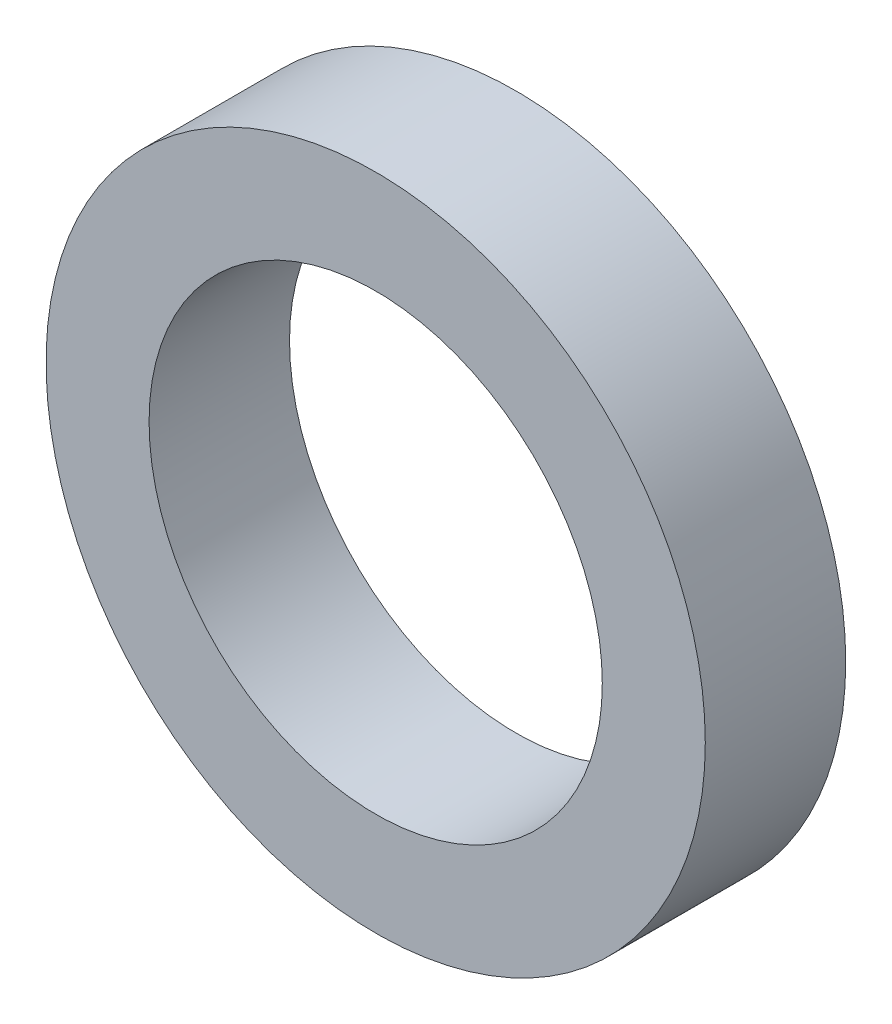
SolidWorks part; units mm, degrees
ref_plane "Front" through (0, 0, 0) normal (0, 0, 1) x (1, 0, 0)
ref_plane "Top" through (0, 0, 0) normal (0, 1, 0) x (1, 0, 0)
ref_plane "Right" through (0, 0, 0) normal (1, 0, 0) x (0, 0, -1)
sketch "Sketch1" plane through (0, 0, 0) normal (0, 0, 1) x (1, 0, 0)
  circle A0 centre (0, 0) radius 6.325
  circle A1 centre (0, 0) radius 9.2
extrude "Boss-Extrude1" add sketch "Sketch1" along normal blind 3.92
